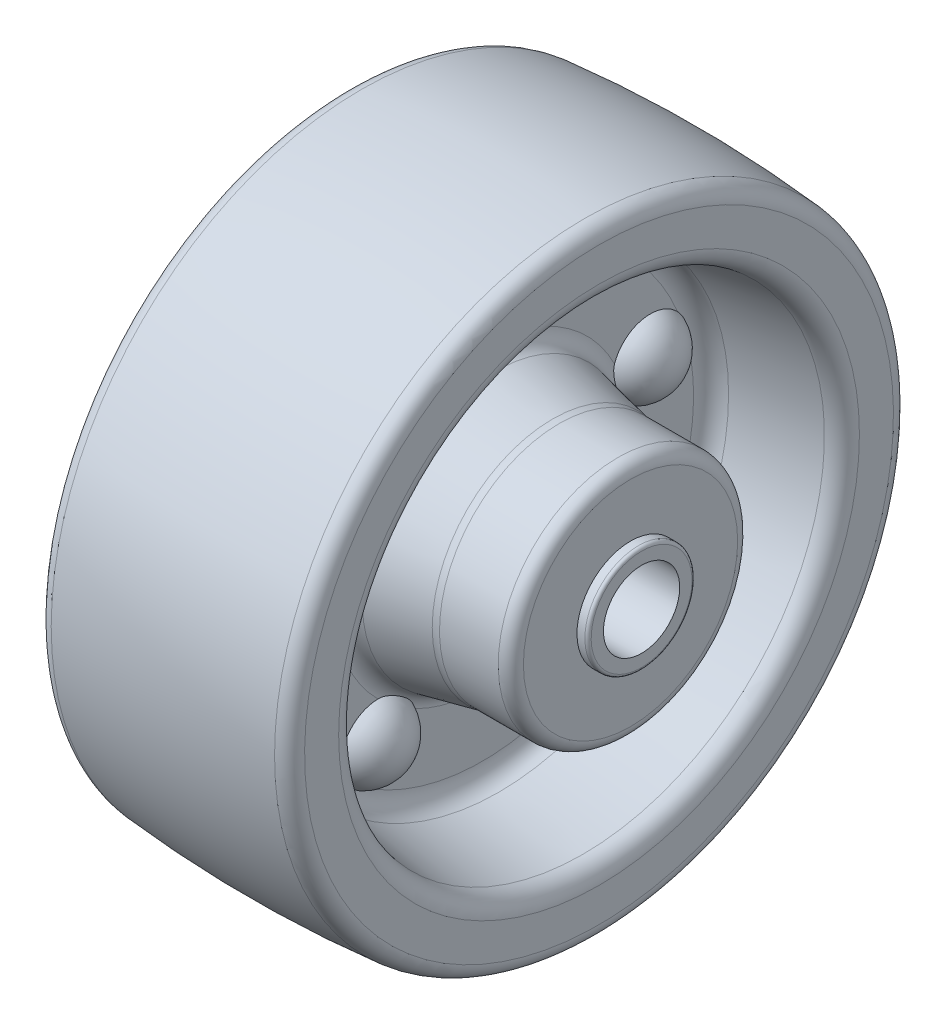
SolidWorks part; units mm, degrees
ref_plane "Front Plane" through (0, 0, 0) normal (0, 0, 1) x (1, 0, 0)
ref_plane "Top Plane" through (0, 0, 0) normal (0, 1, 0) x (1, 0, 0)
ref_plane "Right Plane" through (0, 0, 0) normal (1, 0, 0) x (0, 0, -1)
ref_axis "Axis_X" through (-88.99, 0, 0) along (1, 0, 0)
ref_axis "Axis_Y" through (0, 55, 0) along (0, -1, 0)
ref_axis "Axis_Z" through (0, 0, -88.99) along (0, 0, 1)
sketch "Sketch1" plane through (0, 0, 0) normal (0, 0, 1) x (1, 0, 0)
  line L0 (0, 0) -> (0, 50) construction
  line L1 (0, 0) -> (-25, 0) construction
  line L2 (-20, 38.713) -> (-20, 48.9975)
  line L3 (20, 38.713) -> (20, 48.9975)
  line L4 (-20, 38.713) -> (-1.5, 36.113)
  line L5 (-1.5, 36.113) -> (-1.5, 21.477)
  line L6 (-1.5, 21.477) -> (-13.1534, 19)
  line L7 (-13.1534, 19) -> (-25, 19)
  line L8 (-26.751, 6.05) -> (26.751, 6.05)
  line L9 (-26.751, 6.05) -> (-26.751, 8.5)
  line L10 (-26.751, 8.5) -> (-25, 8.5)
  line L11 (-25, 8.5) -> (-25, 19)
  line L12 (-1.5, 28.795) -> (-20, 28.795) construction
  line L13 (20, 38.713) -> (1.5, 36.113)
  line L14 (1.5, 36.113) -> (1.5, 21.477)
  line L15 (1.5, 21.477) -> (13.1534, 19)
  line L16 (13.1534, 19) -> (25, 19)
  line L17 (25, 19) -> (25, 8.5)
  line L18 (25, 8.5) -> (26.751, 8.5)
  line L19 (26.751, 8.5) -> (26.751, 6.05)
  arc A0 (20, 48.9975) -> (-20, 48.9975) centre (0, -150) ccw
  dimension "FIX_1" = 400
  dimension "B" = 40
  dimension "FIX_9" = 12.1
  dimension "FIX_2" = 53.502
  dimension "FIX_10" = 17
  dimension "FIX_3" = 50
  dimension "FIX_11" = 38
  dimension "FIX_4" = 3
  dimension "FIX_5" = 8
  dimension "FIX_6" = 12
  dimension "FIX_7" = 28.795
  dimension "FIX_8" = 11.287
  dimension "D" = 100
revolve "Revolve1" add sketch "Sketch1" angle 360 about L1
fillet "Fillet1" radius 2.5 4 edges at (1.5, 21.477, 0) (-1.5, 21.477, 0) (20, 48.9975, 0) (-20, 48.9975, 0)
fillet "Fillet2" radius 3 4 edges at (-1.5, 36.113, 0) (1.5, 36.113, 0) (20, 38.713, 0) (-20, 38.713, 0)
fillet "Fillet3" radius 5 2 edges at (13.1534, 19, 0) (-13.1534, 19, 0)
fillet "Fillet4" radius 2 2 edges at (-25, 19, 0) (25, 19, 0)
fillet "Fillet5" radius 0.5 2 edges at (26.751, 8.5, 0) (-26.751, 8.5, 0)
sketch "Sketch2" plane through (0, 0, 0) normal (0, 0, 1) x (1, 0, 0)
  line L0 (-1.5, 28) -> (-1.5354, 28) construction
  line L1 (-1.5, 33.5051) -> (-1.5, -33.5051) construction
  line L2 (-1.5, 28) -> (-5.5, 28)
  line L3 (-1.5, 28) -> (-1.5, 34)
  line L4 (0, 0) -> (0, 50) construction
  line L5 (1.5, 28) -> (1.5, 34)
  line L6 (1.5, 28) -> (5.5, 28)
  arc A0 (-1.5, 34) -> (-5.5, 28) centre (1, 28) ccw
  arc A1 (17.7215, 49.2133) -> (-17.7215, 49.2133) centre (0, -150) ccw construction
  arc A2 (1.5, 34) -> (5.5, 28) centre (-1, 28) cw
  dimension "FIX_18" = 13
  dimension "FIX_19" = 4
  dimension "FIX_20" = 28
revolve "Revolve2" add sketch "Sketch2" angle 360 about L0
pattern_circular "CirPattern1" count 5 every 72 about axis through (-88.99, 0, 0) along (1, 0, 0) of "Revolve2"
ref_plane "Plane1" through (0, -50, 0) normal (0, 1, 0) x (1, 0, 0)
equation "\"Factor\"= 1.082532"
